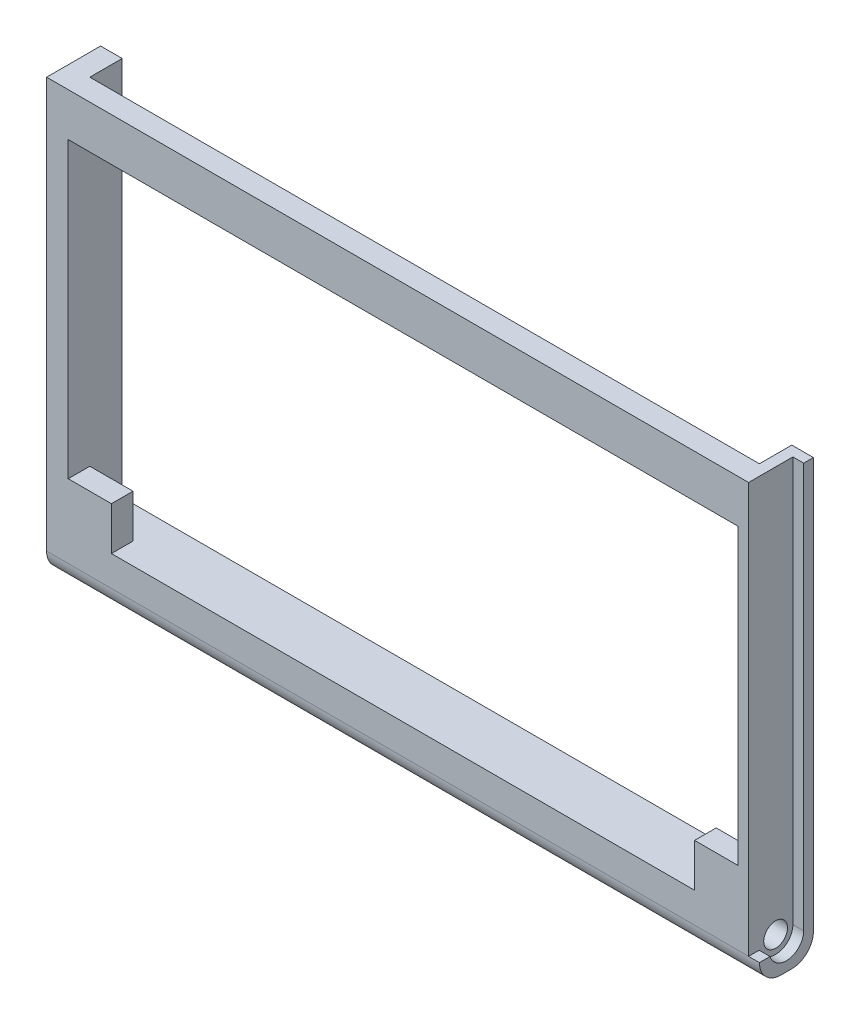
SolidWorks part; units mm, degrees
ref_plane "前视基准面" through (0, 0, 0) normal (0, 0, 1) x (1, 0, 0)
ref_plane "上视基准面" through (0, 0, 0) normal (0, 1, 0) x (1, 0, 0)
ref_plane "右视基准面" through (0, 0, 0) normal (1, 0, 0) x (0, 0, -1)
sketch "草图1" plane through (0, 0, 0) normal (0, 0, 1) x (1, 0, 0)
  line L1 (-16.5, 10) -> (16.5, 10)
  line L2 (-16.5, 10) -> (-16.5, -10)
  line L3 (-16.5, -10) -> (16.5, -10)
  line L4 (16.5, 10) -> (16.5, -10)
  line L5 (-16.5, 10) -> (16.5, -10) construction
  line L6 (-16.5, -10) -> (16.5, 10) construction
  point P0 (0, 0)
  dimension "D1" = 33
  dimension "D2" = 20
extrude "凸台-拉伸1" add sketch "草图1" along normal blind 2.5
sketch "草图2" plane through (0, 0, 2.5) normal (0, 0, 1) x (1, 0, 0)
  line L0 (-16.5, 10) -> (-16.5, -10) construction
  line L1 (-15.5, 10) -> (15.5, 10)
  line L2 (-15.5, 10) -> (-15.5, -7.6)
  line L3 (-15.5, -7.6) -> (15.5, -7.6)
  line L4 (15.5, 10) -> (15.5, -7.6)
  line L5 (16.5, -10) -> (16.5, 10) construction
  line L6 (-16.5, -10) -> (16.5, -10) construction
  line L7 (16.5, 10) -> (-16.5, 10) construction
  dimension "D1" = 1
  dimension "D2" = 1
  dimension "D3" = 2.4
extrude "切除-拉伸1" cut sketch "草图2" against normal blind 2.5
sketch "草图4" plane through (15.5, 0, 0) normal (-1, 0, 0) x (0, 0, 1)
  line L1 (2.5, 10) -> (1.5, 10)
  line L2 (2.5, 10) -> (2.5, 8)
  line L3 (2.5, 8) -> (1.5, 8)
  line L4 (1.5, 10) -> (1.5, 8)
  dimension "D1" = 2
  dimension "D2" = 1
extrude "凸台-拉伸2" add sketch "草图4" along normal blind 31
sketch "草图5" plane through (15.5, 0, 0) normal (-1, 0, 0) x (0, 0, 1)
  line L0 (2.5, -7.6) -> (2.5, 8) construction
  line L1 (2.5, -5.6) -> (1.5, -5.6)
  line L2 (2.5, -5.6) -> (2.5, -7.6)
  line L3 (2.5, -7.6) -> (1.5, -7.6)
  line L4 (1.5, -5.6) -> (1.5, -7.6)
  line L5 (0, -7.6) -> (2.5, -7.6) construction
  dimension "D1" = 1
  dimension "D2" = 2
  dimension "D3" = 0
extrude "凸台-拉伸3" add sketch "草图5" along normal blind 2
sketch "草图6" plane through (-15.5, 0, 0) normal (1, 0, 0) x (0, 0, -1)
  line L0 (-2.5, 8) -> (-2.5, -7.6) construction
  line L1 (-2.5, -5.6) -> (-1.5, -5.6)
  line L2 (-2.5, -5.6) -> (-2.5, -7.6)
  line L3 (-2.5, -7.6) -> (-1.5, -7.6)
  line L4 (-1.5, -5.6) -> (-1.5, -7.6)
  line L5 (0, -7.6) -> (-2.5, -7.6) construction
  dimension "D1" = 1
  dimension "D2" = 2
  dimension "D3" = 0
extrude "凸台-拉伸4" add sketch "草图6" along normal blind 2
sketch "草图7" plane through (-16.5, 0, 0) normal (-1, 0, 0) x (0, 0, 1)
  line L0 (2.5, -10) -> (0, -10) construction
  line L1 (2.5, 10) -> (2.5, -10) construction
  circle A0 centre (1.25, -8.75) radius 0.55
  dimension "D1" = 1.1
  dimension "D2" = 1.25
  dimension "D3" = 1.25
extrude "切除-拉伸2" cut sketch "草图7" against normal through all
fillet "圆角3" radius 1 1 edges at (0, -10, 0)
fillet "圆角4" radius 1 1 edges at (0, -10, 2.5)
sketch "草图8" plane through (16.5, 0, 0) normal (1, 0, 0) x (0, 0, -1)
  circle A0 centre (-1.25, -8.75) radius 0.8
  dimension "D1" = 1.6
extrude "切除-拉伸3" cut sketch "草图8" against normal blind 0.5
sketch "草图9" plane through (16.5, 0, 0) normal (1, 0, 0) x (0, 0, -1)
  line L0 (-0.45, -8.75) -> (-0.45, 10)
  line L1 (-2.5, 10) -> (0, 10) construction
  line L2 (-0.45, 10) -> (-2.5, 10)
  line L3 (-2.5, 10) -> (-2.5, -9)
  line L4 (-2.5, -9) -> (-2.0099, -9)
  circle A0 centre (-1.25, -8.75) radius 0.8 construction
  circle A1 centre (-1.25, -8.75) radius 0.8 construction
  arc A2 (-0.45, -8.75) -> (-2.0099, -9) centre (-1.25, -8.75) ccw
extrude "切除-拉伸4" cut sketch "草图9" against normal blind 0.5
